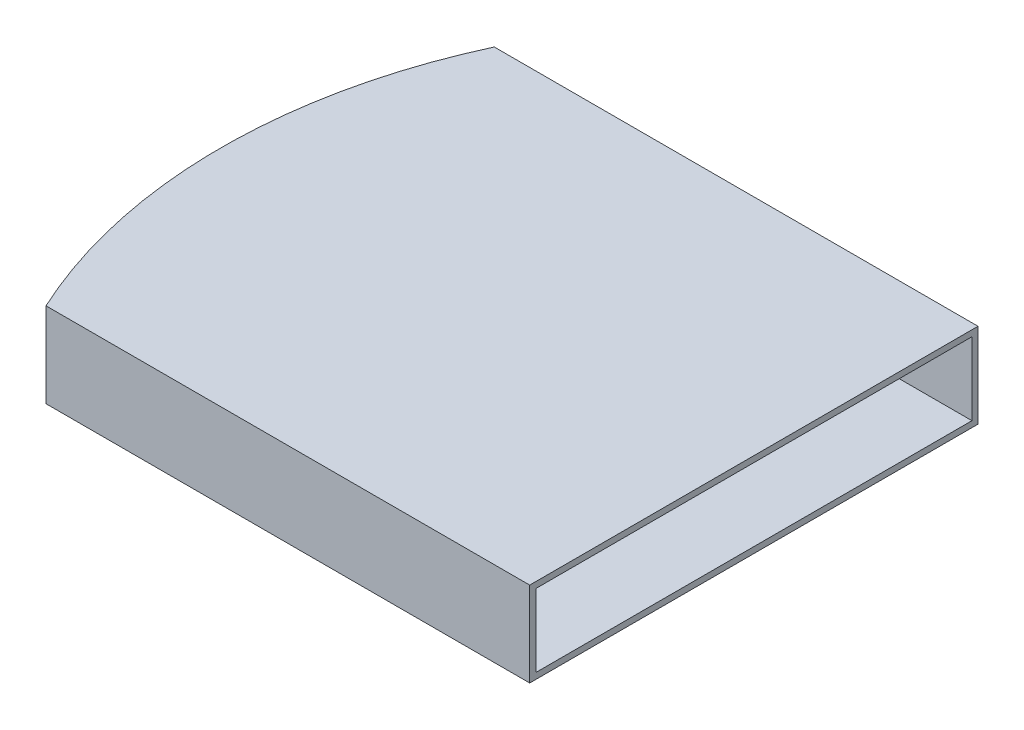
SolidWorks part; units mm, degrees
ref_plane "Front Plane" through (0, 0, 0) normal (0, 0, 1) x (1, 0, 0)
ref_plane "Top Plane" through (0, 0, 0) normal (0, 1, 0) x (1, 0, 0)
ref_plane "Right Plane" through (0, 0, 0) normal (1, 0, 0) x (0, 0, -1)
sketch "Sketch1" plane through (0, 0, 0) normal (0, 1, 0) x (1, 0, 0)
  line L1 (-253.5034, 234.95) -> (0, 234.95)
  line L3 (-253.5034, 0) -> (0, 0)
  line L4 (0, 234.95) -> (0, 0)
  line L5 (-253.5034, 234.95) -> (0, 0) construction
  line L6 (-253.5034, 0) -> (0, 234.95) construction
  arc A0 (-253.5034, 234.95) -> (-253.5034, 0) centre (0, 117.475) ccw
  point P4 (-126.7517, 117.475)
  point P5 (-279.4, 117.475)
  dimension "D2" = 279.4
  dimension "D1" = 234.95
  dimension "D3" = 279.4
extrude "Boss-Extrude1" add sketch "Sketch1" along normal blind 44.45
ref_plane "Plane1" through (0, 0, -3.175) normal (0, 0, 1) x (1, 0, 0)
sketch "Sketch2" plane through (0, 0, -3.175) normal (0, 0, 1) x (1, 0, 0)
  line L0 (-247.1534, 41.275) -> (-215.1837, 3.175)
  line L1 (-247.1534, 41.275) -> (32.8376, 41.275)
  line L3 (-215.1837, 3.175) -> (32.8376, 3.175)
  line L4 (32.8376, 41.275) -> (32.8376, 3.175)
  line L5 (-253.5034, 44.45) -> (0, 44.45) construction
  line L7 (-253.5034, 44.45) -> (-253.5034, 0) construction
  point P2 (0, 0)
  point P4 (-171.2671, 5.128)
  point P8 (-218.4608, 44.45)
  point P9 (0, 0)
  dimension "D1" = 50
  dimension "D2" = 38.1
  dimension "D3" = 3.175
  dimension "D4" = 6.35
extrude "Cut-Extrude2" cut sketch "Sketch2" against normal blind 228.6
